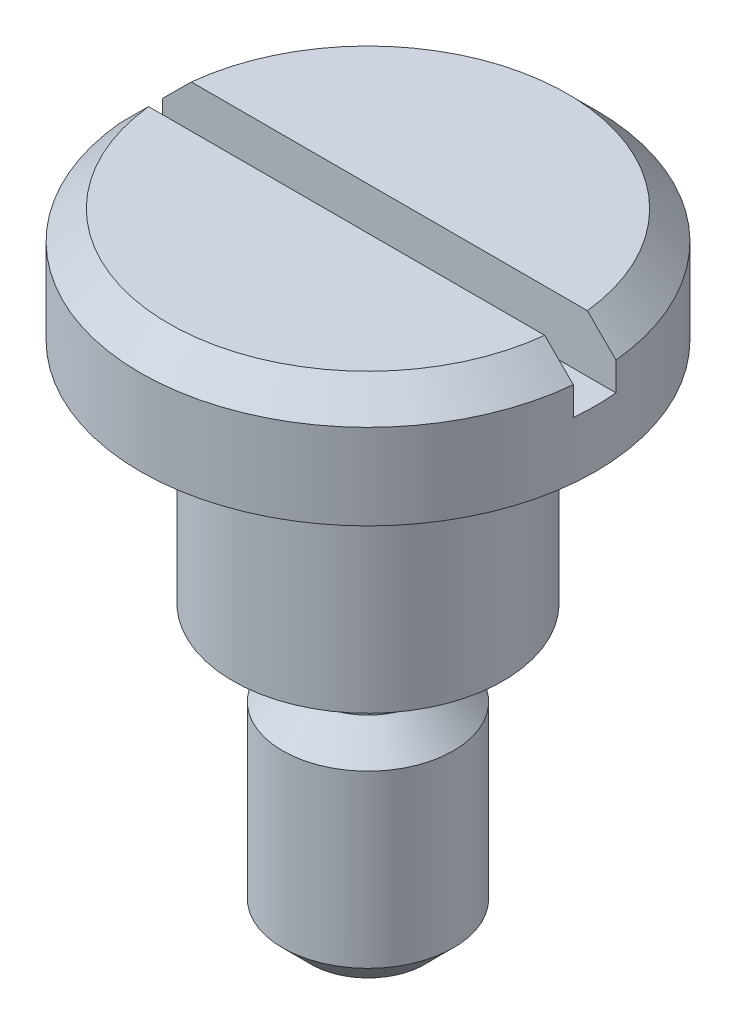
SolidWorks part; units mm, degrees
material "AISI 1045 钢，冷拔"
ref_plane "前视基准面" through (0, 0, 0) normal (0, 0, 1) x (1, 0, 0)
ref_plane "上视基准面" through (0, 0, 0) normal (0, 1, 0) x (1, 0, 0)
ref_plane "右视基准面" through (0, 0, 0) normal (1, 0, 0) x (0, 0, -1)
sketch "草图1" plane through (0, 0, 0) normal (0, 0, 1) x (1, 0, 0)
  line L0 (0, 0) -> (3, 0)
  line L1 (3, 0) -> (3, 8)
  line L2 (3, 8) -> (2, 8)
  line L3 (2, 8) -> (2, 10)
  line L4 (2, 10) -> (4.75, 10)
  line L5 (4.75, 10) -> (4.75, 18)
  line L6 (4.75, 18) -> (8, 18)
  line L7 (8, 18) -> (8, 22)
  line L8 (8, 22) -> (0, 22)
  line L9 (0, 22) -> (0, 0)
  dimension "D1" = 22
  dimension "D2" = 10
  dimension "D3" = 8
  dimension "D4" = 4.75
  dimension "D5" = 8
  dimension "D6" = 3
  dimension "D7" = 1
  dimension "D8" = 2
revolve "旋转1" add sketch "草图1" angle 360 about L9
chamfer "倒角2" distance 1 angle 45 3 edges at (-3, 0, 0) (-8, 22, 0) (-3, 8, 0)
sketch "草图2" plane through (0, 22, 0) normal (0, 1, 0) x (1, 0, 0)
  line L0 (-7.9648, -0.75) -> (7.9648, -0.75)
  line L1 (-7.9648, 0.75) -> (7.9648, 0.75)
  circle A0 centre (0, 0) radius 8 construction
  arc A1 (-7.9648, 0.75) -> (-7.9648, -0.75) centre (0, 0) ccw
  arc A2 (7.9648, -0.75) -> (7.9648, 0.75) centre (0, 0) ccw
  dimension "D1" = 0.75
  dimension "D2" = 0.75
extrude "切除-拉伸1" cut sketch "草图2" against normal blind 2
